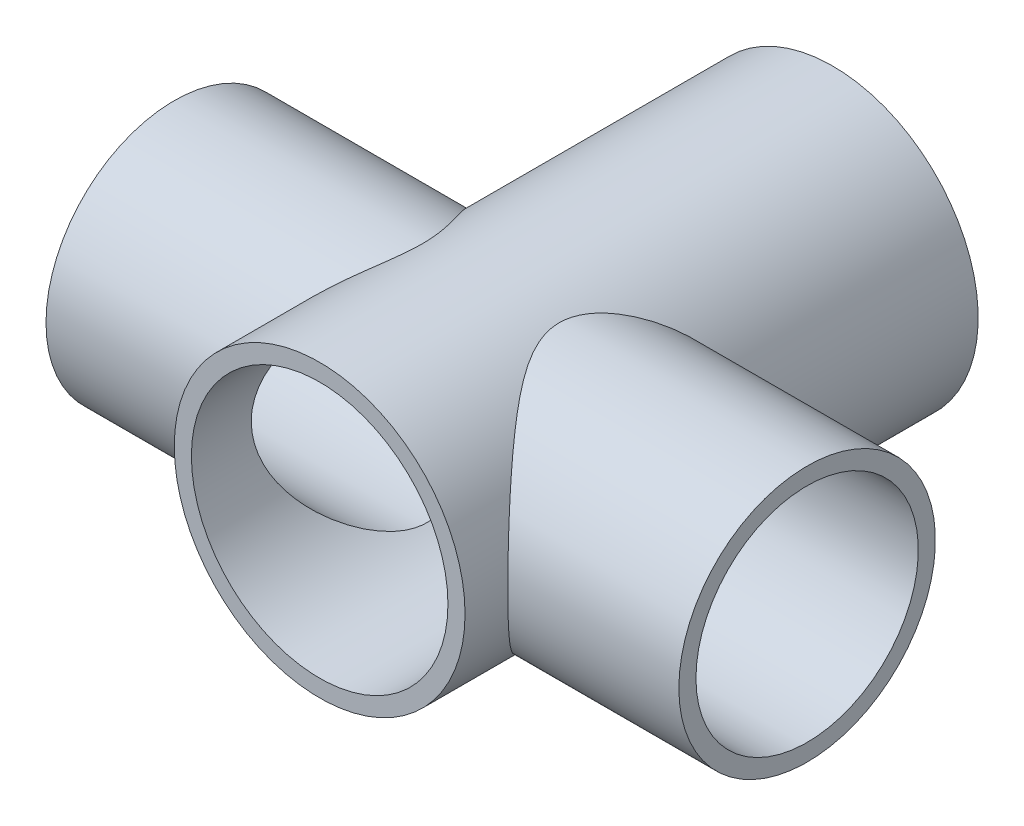
SolidWorks part; units mm, degrees
ref_plane "Front Plane" through (0, 0, 0) normal (0, 0, 1) x (1, 0, 0)
ref_plane "Top Plane" through (0, 0, 0) normal (0, 1, 0) x (1, 0, 0)
ref_plane "Right Plane" through (0, 0, 0) normal (1, 0, 0) x (0, 0, -1)
sketch "Sketch1" plane through (0, 0, 0) normal (0, 0, 1) x (1, 0, 0)
  line L0 (0, 0) -> (0, -50000) construction
  circle A0 centre (0, 0) radius 15
  circle A1 centre (0, 0) radius 17
extrude "Boss-Extrude1" add sketch "Sketch1" along normal blind 40
ref_plane "Plane1" through (-17, 0, 0) normal (-1, 0, 0) x (0, 0, 1)
sketch "Sketch2" plane through (-17, 0, 0) normal (-1, 0, 0) x (0, 0, 1)
  line L0 (0, 17) -> (0, -17) construction
  circle A0 centre (20, 0) radius 15
  dimension "D2" = 30
  dimension "D1" = 20
extrude "Boss-Extrude2" add sketch "Sketch2" against normal up to surface and the other way blind 20 contours A0 up to face at (17, 0, 40)
mirror "Mirror1" about plane through (0, 0, 0) normal (1, 0, 0) of "Boss-Extrude2"
sketch "Sketch3" plane through (-37, 0, 0) normal (-1, 0, 0) x (0, 0, 1)
  circle A0 centre (20, 0) radius 13
  circle A1 centre (20, 0) radius 15 construction
  dimension "D2" = 26
  dimension "D1" = 0
extrude "Cut-Extrude1" cut sketch "Sketch3" against normal through all both and the other way through all
sketch "Sketch5" plane through (0, 0, 0) normal (0, 0, -1) x (-1, 0, 0)
  circle A0 centre (0, 0) radius 15
  circle A1 centre (0, 0) radius 17
extrude "Boss-Extrude3" add sketch "Sketch5" along normal blind 20
